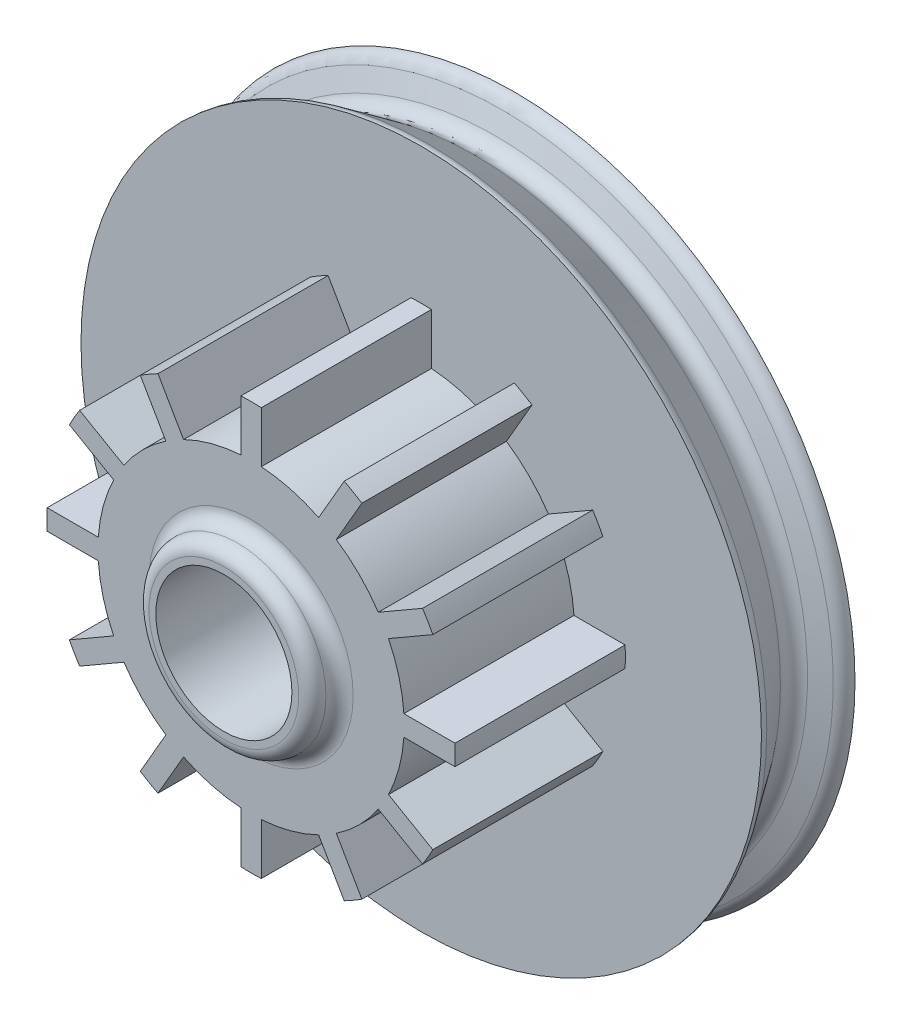
SolidWorks part; units mm, degrees
ref_plane "Front Plane" through (0, 0, 0) normal (0, 0, 1) x (1, 0, 0)
ref_plane "Top Plane" through (0, 0, 0) normal (0, 1, 0) x (1, 0, 0)
ref_plane "Right Plane" through (0, 0, 0) normal (1, 0, 0) x (0, 0, -1)
sketch "Sketch2" plane through (0, 0, 0) normal (1, 0, 0) x (0, 0, -1)
  line L0 (0, 4) -> (-15.5, 4)
  line L1 (-15.5, 4) -> (-15.5, 12)
  line L2 (-15.5, 12) -> (-5.5, 12)
  line L3 (-5.5, 12) -> (-5.5, 20)
  line L4 (-5.0411, 19.8553) -> (-2.3662, 17.9823)
  line L5 (-1.1556, 18.364) -> (-0.7518, 19.4736)
  line L6 (0, 20) -> (0, 4)
  line L7 (-15.5, 25) -> (-5.5, 25) construction
  line L8 (0, 0) -> (-45.1775, 0) construction
  arc A0 (-5.5, 20) -> (-5.0411, 19.8553) centre (-5.5, 19.2) cw
  arc A1 (-2.3662, 17.9823) -> (-1.1556, 18.364) centre (-1.9074, 18.6376) ccw
  arc A2 (-0.7518, 19.4736) -> (0, 20) centre (0, 19.2) cw
  point P13 (-2.4785, 15.8229)
  dimension "D1" = 15.5
  dimension "D8" = 0.8
  dimension "D2" = 4
  dimension "D3" = 20
  dimension "D4" = 20
  dimension "D5" = 5.5
  dimension "D6" = 8
  dimension "D9" = 55
revolve "Revolve1" add sketch "Sketch2" angle 360 about L8
sketch "Sketch3" plane through (0, 0, 15.5) normal (0, 0, 1) x (1, 0, 0)
  line L0 (0, 20) -> (0, 0) construction
  line L1 (0, 0) -> (10, 17.3205) construction
  line L2 (0.6, 19.991) -> (0.6, 2.2392)
  line L3 (0.6, 2.2392) -> (9.4759, 17.6127)
  circle A0 centre (0, 0) radius 20 construction
  arc A1 (9.4759, 17.6127) -> (0.6, 19.991) centre (0.6, 2.2392) ccw
  arc A2 (0.6, 8.98) -> (3.9704, 8.0769) centre (0, 0) cw
  circle A3 centre (0, 0) radius 12 construction
  circle A4 centre (0, 0) radius 4 construction
  circle M6 centre (0, 0) radius 12
  dimension "D2" = 1.2
  dimension "D4" = 5
  dimension "D1" = 30
  dimension "D3" = 1.2
extrude "Cut-Extrude1" cut sketch "Sketch3" against normal up to surface (10 mm away) contours L2 A2 L3 M6 | L3 A1 L2 M6 region at (2.7221, 10.1589, 15.5) region at (4.2131, 15.7237, 15.5) up to face at (-12, 0, 5.5)
ref_axis "Axis1" through (0, 0, 15.5) along (0, 0, -1)
pattern_circular "CirPattern1" count 12 over 360 about axis through (0, 0, 15.5) along (0, 0, -1) of "Cut-Extrude1"
sketch "Sketch4" plane through (0, 0, 0) normal (0, 0, -1) x (-1, 0, 0)
  circle A0 centre (0, 0) radius 14
  circle A1 centre (0, 0) radius 7
  dimension "D1" = 14
  dimension "D2" = 28
extrude "Cut-Extrude2" cut sketch "Sketch4" against normal offset from surface (3.1 mm away) 2.4
fillet "Fillet1" radius 1 4 edges at (7, 0, 3.1) (14, 0, 3.1) (-7, 0, 0) (-14, 0, 0)
sketch "Sketch5" plane through (0, 0, 15.5) normal (0, 0, 1) x (1, 0, 0)
  circle A0 centre (0, 0) radius 4
  circle A1 centre (0, 0) radius 5.2
  circle A2 centre (0, 0) radius 4 construction
  dimension "D1" = 1.2
extrude "Boss-Extrude1" add sketch "Sketch5" along normal blind 1.6
fillet "Fillet2" radius 0.8 2 edges at (5.2, 0, 15.5) (5.2, 0, 17.1)
